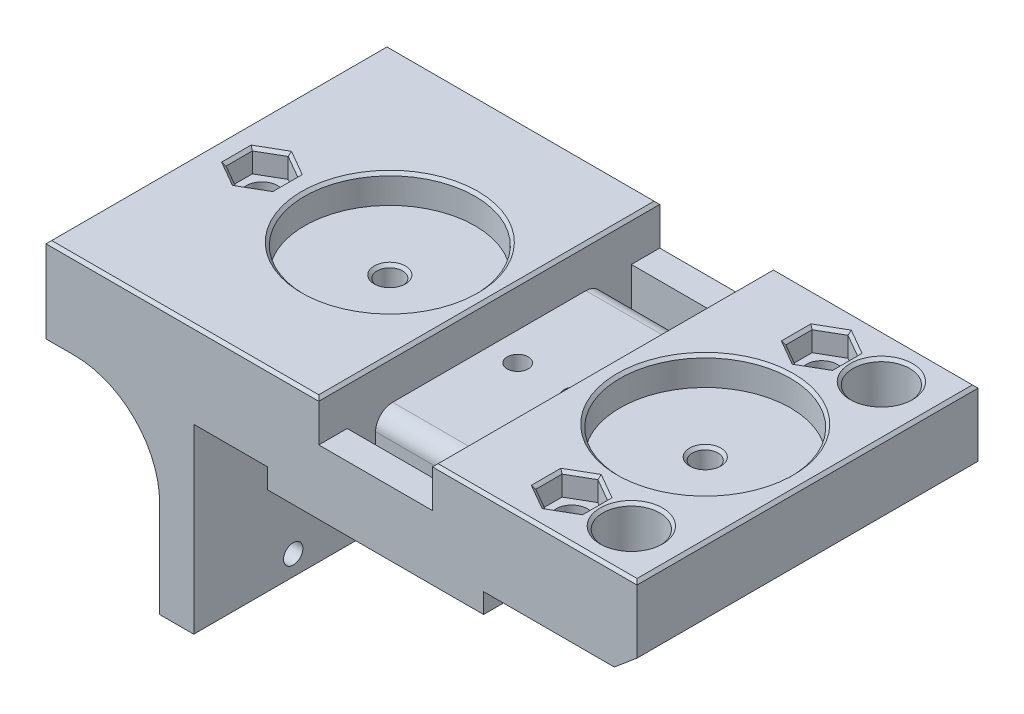
SolidWorks part; units mm, degrees
ref_plane "Front Plane" through (0, 0, 0) normal (0, 0, 1) x (1, 0, 0)
ref_plane "Top Plane" through (0, 0, 0) normal (0, 1, 0) x (1, 0, 0)
ref_plane "Right Plane" through (0, 0, 0) normal (1, 0, 0) x (0, 0, -1)
sketch "Sketch1" plane through (0, 0, 0) normal (0, 1, 0) x (1, 0, 0)
  line L1 (0, 0) -> (84, 0)
  line L2 (0, 0) -> (0, 60)
  line L3 (0, 60) -> (84, 60)
  line L4 (84, 0) -> (84, 60)
  dimension "D1" = 84
  dimension "D2" = 60
extrude "Boss-Extrude1" add sketch "Sketch1" along normal blind 15
sketch "Sketch2" plane through (0, 0, 0) normal (0, -1, 0) x (1, 0, 0)
  line L0 (0, 0) -> (84, 0) construction
  line L1 (0, -60) -> (6, -60)
  line L2 (0, -60) -> (0, 0)
  line L3 (0, 0) -> (6, 0)
  line L4 (6, -60) -> (6, 0)
  dimension "D1" = 6
extrude "Boss-Extrude2" add sketch "Sketch2" along normal blind 32
sketch "Sketch3" plane through (0, 0, 0) normal (-1, 0, 0) x (0, 0, 1)
  line L0 (0, -16) -> (-60, -16) construction
  line L1 (0, 15) -> (0, -32) construction
  line L2 (-60, 15) -> (-60, -32) construction
  line L5 (-60, -32) -> (-60, 0) construction
  line L6 (-17.5, -3.5) -> (-42.5, -3.5)
  line L7 (-17.5, -3.5) -> (-17.5, -28.5)
  line L8 (-17.5, -28.5) -> (-42.5, -28.5)
  line L9 (-42.5, -3.5) -> (-42.5, -28.5)
  line L10 (-17.5, -3.5) -> (-42.5, -28.5) construction
  line L11 (-17.5, -28.5) -> (-42.5, -3.5) construction
  point P7 (-30, -16)
  dimension "D1" = 25
hole_wizard "M3 Clearance Hole1" positions "Sketch4" profile "Sketch5" hole size "M3" standard "ANSI Metric" end condition through all
sketch "Sketch4" plane through (0, 0, 0) normal (-1, 0, 0) x (0, 0, 1)
  point P0 (-42.5, -28.5)
  point P3 (-42.5, -3.5)
  point P6 (-17.5, -3.5)
  point P9 (-17.5, -28.5)
sketch "Sketch5" plane through (0, -28.5, -42.5) normal (0, 1, 0) x (0, 0, 1)
  line L0 (0, 0) -> (0, 84)
  line L1 (0, 84) -> (1.7, 84)
  line L2 (1.7, 84) -> (1.7, 0)
  line L5 (1.7, 0) -> (0, 0)
  line L11 (0, -6.35) -> (0, 107.95) construction
  dimension "Thru Hole Dia." = 3.4
  dimension "Thru Hole Depth" = 84
ref_plane "Plane1" through (0, -16, 0) normal (0, -1, 0) x (-1, 0, 0)
ref_plane "Plane2" through (0, -4.5, 0) normal (0, -1, 0) x (-1, 0, 0)
ref_plane "Plane5" through (0, 8.2324, 0) normal (0, -1, 0) x (-1, 0, 0)
ref_plane "Belt Plane" through (0, -3.5, 0) normal (0, -1, 0) x (-1, 0, 0)
ref_plane "Plane6" through (0, 7.8524, 0) normal (0, -1, 0) x (-1, 0, 0)
sketch "Sketch7" plane through (0, 0, 0) normal (0, -1, 0) x (1, 0, 0)
  line L0 (84, -60) -> (6, -60) construction
  line L1 (19, -60) -> (57, -60)
  line L2 (19, -60) -> (19, 0)
  line L3 (19, 0) -> (57, 0)
  line L4 (57, -60) -> (57, 0)
  line L5 (6, 0) -> (84, 0) construction
  line L6 (6, -60) -> (6, 0) construction
  line L8 (84, 0) -> (84, -60) construction
  dimension "D1" = 13
  dimension "D2" = 27
extrude "Boss-Extrude3" add sketch "Sketch7" along normal up to surface (3.5 mm away) up to plane "Belt Plane"
sketch "Sketch8" plane through (0, -3.5, 0) normal (0, -1, 0) x (1, 0, 0)
  line L0 (42, -60) -> (42, 0) construction
  line L1 (19, -60) -> (57, -60) construction
  line L2 (57, 0) -> (19, 0) construction
  line L3 (34, -60) -> (34, 0) construction
  line L4 (6, -60) -> (6, 0) construction
  dimension "D1" = 36
  dimension "D2" = 8
sketch "Sketch26" plane through (0, 15, 0) normal (0, 1, 0) x (1, 0, 0)
  line L0 (0, 0) -> (84, 0) construction
  line L1 (28, 0) -> (48, 0)
  line L2 (28, 0) -> (28, 60)
  line L3 (28, 60) -> (48, 60)
  line L4 (48, 0) -> (48, 60)
  line L5 (84, 60) -> (0, 60) construction
  line L6 (34, 60) -> (34, 0) construction
  line L7 (42, 60) -> (42, 0) construction
  dimension "D1" = 6
  dimension "D2" = 6
  dimension "D3" = 20
extrude "Cut-Extrude5" cut sketch "Sketch26" against normal up to surface (7.1476 mm away) up to plane "Plane6"
sketch "Sketch30" plane through (0, 0, 0) normal (-1, 0, 0) x (0, 0, 1)
  line L0 (0, 15) -> (0, -32) construction
  line L1 (-60, 15) -> (0, 15)
  line L2 (-60, 15) -> (-60, 0)
  line L3 (-60, 0) -> (0, 0)
  line L4 (0, 15) -> (0, 0)
  dimension "D1" = 15
extrude "Boss-Extrude4" add sketch "Sketch30" along normal blind 20
sketch "Sketch27" plane through (0, 7.8524, 0) normal (0, 1, 0) x (1, 0, 0)
  line L1 (28, 5) -> (48, 5)
  line L2 (28, 5) -> (28, 10)
  line L3 (28, 10) -> (48, 10)
  line L4 (28, 60) -> (28, 0)
  line L5 (28, 0) -> (48, 0)
  line L6 (48, 0) -> (48, 60)
  line L7 (48, 60) -> (28, 60)
  line L8 (28, 60) -> (28, 0) construction
  line L9 (28, 0) -> (48, 0) construction
  line L10 (48, 0) -> (48, 60) construction
  line L11 (48, 60) -> (28, 60) construction
  line L12 (48, 5) -> (48, 10)
  line L13 (48, 50) -> (28, 50)
  line L14 (48, 50) -> (48, 55)
  line L15 (48, 55) -> (28, 55)
  line L16 (28, 50) -> (28, 55)
  dimension "D2" = 5
  dimension "D3" = 5
  dimension "D4" = 5
  dimension "D5" = 5
  dimension "D1" = 0
extrude "Cut-Extrude6" cut sketch "Sketch27" against normal through all
fillet "Fillet1" radius 3 4 edges at (38, -3.5, -55) (38, -3.5, -5) (38, 7.8524, -50) (38, 7.8524, -10)
sketch "Sketch28" plane through (0, 7.8524, 0) normal (0, 1, 0) x (1, 0, 0)
  line L0 (42, 60) -> (42, 0) construction
  line L1 (34, 60) -> (34, 0) construction
  line L2 (42, 60) -> (42, 0) construction
  line L3 (34, 60) -> (34, 0) construction
  line L4 (28, 47) -> (28, 13) construction
  line L5 (48, 13) -> (48, 47) construction
  line L6 (43, 30) -> (34, 30) construction
  circle A0 centre (33, 30) radius 1.85
  circle A1 centre (43, 30) radius 1.85
  dimension "D1" = 3.7
  dimension "D2" = 5
  dimension "D3" = 5
extrude "Cut-Extrude7" cut sketch "Sketch28" against normal through all
ref_plane "Plane4" through (42, 0, 0) normal (-1, 0, 0) x (0, 0, 1)
sketch "Sketch15" plane through (0, 15, 0) normal (0, 1, 0) x (1, 0, 0)
  line L0 (75, 60) -> (75, 0) construction
  line L1 (84, 60) -> (48, 60) construction
  line L2 (48, 0) -> (84, 0) construction
  line L3 (84, 0) -> (84, 60) construction
  point P8 (75, 52)
  point P9 (75, 8)
  dimension "D1" = 9
  dimension "D2" = 8
  dimension "D3" = 8
hole_wizard "CBORE for M5 SHCS2" positions "Sketch18" profile "Sketch19" counterbore size "M5" standard "ANSI Metric" end condition through all
sketch "Sketch18" plane through (0, 15, 0) normal (0, 1, 0) x (1, 0, 0)
  point P0 (75, 52)
  point P3 (75, 8)
sketch "Sketch19" plane through (75, 15, -52) normal (1, 0, 0) x (0, 0, 1)
  line L0 (0, 0) -> (0, 47)
  line L1 (0, 47) -> (2.75, 47)
  line L3 (2.75, 47) -> (2.75, 10)
  line L4 (2.75, 10) -> (5, 10)
  line L5 (5, 10) -> (5, 0)
  line L7 (5, 0) -> (0, 0)
  line L11 (0, -6.35) -> (0, 107.95) construction
  dimension "Thru Hole Dia." = 5.5
  dimension "Thru Hole Depth" = 47
  dimension "C'Bore Dia." = 10
  dimension "C'Bore Depth" = 10
chamfer "Chamfer1" distance 4 angle 40 1 edges at (84, 0, -30) first distance on face at (75, 0, -54.75)
sketch "Sketch21" plane through (0, 0, 0) normal (0, -1, 0) x (1, 0, 0)
  line L24 (64.5, -56.6188) -> (64.5, -47.3812)
  line L25 (64.5, -12.6188) -> (64.5, -3.3812)
  line L26 (-12, -34.6188) -> (-12, -25.3812)
  line L27 (75, -8) -> (64.5, -8) construction
  line L28 (75, -52) -> (64.5, -52) construction
  line L29 (-20, -30) -> (-12, -30) construction
  line L30 (-20, 0) -> (-20, -60) construction
  dimension "D2" = 9.2376
  dimension "D3" = 9.2376
  dimension "D4" = 10.5
  dimension "D1" = 8
hole_wizard "CBORE for M5 SHCS3" positions "Sketch22" profile "Sketch23" counterbore size "M5" standard "ANSI Metric" end condition through all
sketch "Sketch22" plane through (0, 0, 0) normal (0, -1, 0) x (-1, 0, 0)
  line L0 (-64.5, 12.6188) -> (-64.5, 3.3812) construction
  line L1 (-64.5, 56.6188) -> (-64.5, 47.3812) construction
  line L2 (12, 34.6188) -> (12, 25.3812) construction
  point P0 (-64.5, 52)
  point P2 (-64.5, 8)
  point P11 (12, 30)
sketch "Sketch23" plane through (64.5, 0, -52) normal (1, 0, 0) x (0, 0, -1)
  line L0 (0, 0) -> (0, 15)
  line L1 (0, 15) -> (2.75, 15)
  line L3 (2.75, 15) -> (2.75, 5)
  line L4 (2.75, 5) -> (5, 5)
  line L5 (5, 5) -> (5, 0)
  line L7 (5, 0) -> (0, 0)
  line L11 (0, -6.35) -> (0, 107.95) construction
  dimension "Thru Hole Dia." = 5.5
  dimension "Thru Hole Depth" = 15
  dimension "C'Bore Dia." = 10
  dimension "C'Bore Depth" = 5
sketch "Sketch20" plane through (0, 15, 0) normal (0, 1, 0) x (1, 0, 0)
  line L0 (64.5, 0) -> (64.5, 60) construction
  line L1 (48, 0) -> (84, 0) construction
  line L2 (84, 60) -> (48, 60) construction
  line L3 (64.5, 60) -> (-12, 30) construction
  line L5 (-12, 30) -> (64.5, 0) construction
  line L8 (64.5, 12.6188) -> (60.5, 10.3094)
  line L9 (60.5, 10.3094) -> (60.5, 5.6906)
  line L10 (60.5, 5.6906) -> (64.5, 3.3812)
  line L11 (64.5, 3.3812) -> (68.5, 5.6906)
  line L12 (68.5, 5.6906) -> (68.5, 10.3094)
  line L13 (68.5, 10.3094) -> (64.5, 12.6188)
  line L14 (64.5, 47.3812) -> (68.5, 49.6906)
  line L15 (68.5, 49.6906) -> (68.5, 54.3094)
  line L16 (68.5, 54.3094) -> (64.5, 56.6188)
  line L17 (64.5, 56.6188) -> (60.5, 54.3094)
  line L18 (60.5, 54.3094) -> (60.5, 49.6906)
  line L19 (60.5, 49.6906) -> (64.5, 47.3812)
  line L20 (-8, 27.6906) -> (-8, 32.3094)
  line L21 (-8, 32.3094) -> (-12, 34.6188)
  line L22 (-12, 34.6188) -> (-16, 32.3094)
  line L23 (-16, 32.3094) -> (-16, 27.6906)
  line L24 (-16, 27.6906) -> (-12, 25.3812)
  line L25 (-12, 25.3812) -> (-8, 27.6906)
  circle A0 centre (64.5, 8) radius 4 construction
  circle A1 centre (64.5, 52) radius 4 construction
  circle A2 centre (-12, 30) radius 4 construction
  circle A3 centre (64.5, 52) radius 2.75 construction
  dimension "D2" = 8
  dimension "D4" = 8
extrude "Cut-Extrude8" cut sketch "Sketch20" against normal blind 4
chamfer "Chamfer2" distance 0.5 angle 45 28 edges at (4, 15, -60) (28, 15, -30) (4, 15, 0) (84, 15, -30) (66, 15, 0) (48, 15, -30) (66, 15, -60) (75, 15, -3) (75, 15, -47) (-20, 15, -30) (-10, 15, -33.4641) (-14, 15, -33.4641) (-16, 15, -30) (-14, 15, -26.5359) (-10, 15, -26.5359) (-8, 15, -30) (66.5, 15, -55.4641) (62.5, 15, -55.4641) (60.5, 15, -52) (62.5, 15, -48.5359) (66.5, 15, -48.5359) (60.5, 15, -8) (62.5, 15, -4.5359) (66.5, 15, -4.5359) (66.5, 15, -11.4641) (62.5, 15, -11.4641) (68.5, 15, -8) (68.5, 15, -52)
sketch "Sketch31" plane through (0, 15, 0) normal (0, 1, 0) x (1, 0, 0)
  line L0 (48.5, 30) -> (83.5, 30) construction
  line L1 (48.5, 59.5) -> (48.5, 0.5) construction
  line L2 (83.5, 0.5) -> (83.5, 59.5) construction
  line L3 (27.5, 0.5) -> (27.5, 59.5) construction
  circle A0 centre (66, 30) radius 15
  circle A1 centre (10.5, 30) radius 15
  dimension "D1" = 30
  dimension "D2" = 17
extrude "Cut-Extrude9" cut sketch "Sketch31" against normal blind 5
sketch "Sketch32" plane through (0, 10, 0) normal (0, 1, 0) x (1, 0, 0)
  circle A0 centre (10.5, 30) radius 2.25
  circle A1 centre (66, 30) radius 2.25
  circle A2 centre (66, 30) radius 15 construction
  circle A3 centre (10.5, 30) radius 15 construction
  dimension "D1" = 4.5
extrude "Cut-Extrude10" cut sketch "Sketch32" against normal through all
chamfer "Chamfer3" distance 0.5 angle 45 4 edges at (10.5, 15, -15) (66, 15, -15) (66, 10, -27.75) (10.5, 10, -27.75)
sketch "Sketch33" plane through (0, 0, 0) normal (-1, 0, 0) x (0, 0, 1)
  circle A0 centre (-17.5, -3.5) radius 3
  circle A1 centre (-42.5, -3.5) radius 3
  dimension "D1" = 6
fillet "Fillet2" radius 15 1 edges at (0, 0, -30)
extrude "Cut-Extrude11" cut sketch "Sketch33" along normal through all
